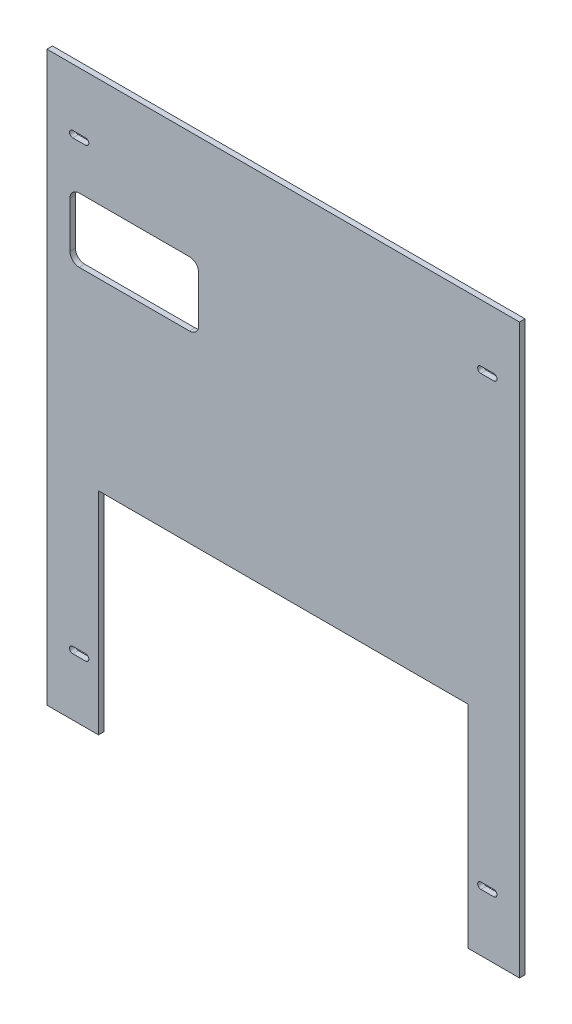
SolidWorks part; units mm, degrees
ref_plane "Plan de face" through (0, 0, 0) normal (0, 0, 1) x (1, 0, 0)
ref_plane "Plan de dessus" through (0, 0, 0) normal (0, 1, 0) x (1, 0, 0)
ref_plane "Plan de droite" through (0, 0, 0) normal (1, 0, 0) x (0, 0, -1)
sketch "Esquisse1" plane through (0, 0, 0) normal (0, 0, 1) x (1, 0, 0)
  line L0 (0, 154.5) -> (0, -154.5) construction
  line L1 (128.5, 154.5) -> (-128.5, 154.5)
  line L2 (128.5, 154.5) -> (128.5, -154.5)
  line L3 (128.5, -154.5) -> (-128.5, -154.5)
  line L4 (-128.5, 154.5) -> (-128.5, -154.5)
  line L5 (128.5, 154.5) -> (-128.5, -154.5) construction
  line L6 (128.5, -154.5) -> (-128.5, 154.5) construction
  line L7 (-111, 121.5) -> (0, 121.5) construction
  line L8 (-128.5, 0) -> (128.5, 0) construction
  line L9 (-114.5, 121.5) -> (-107.5, 121.5) construction
  line L10 (-114.5, 123.25) -> (-107.5, 123.25)
  line L11 (-114.5, 119.75) -> (-107.5, 119.75)
  line L12 (107.5, -121.5) -> (114.5, -121.5) construction
  line L13 (107.5, -119.75) -> (114.5, -119.75)
  line L14 (107.5, -123.25) -> (114.5, -123.25)
  line L15 (-114.5, -121.5) -> (-107.5, -121.5) construction
  line L16 (-114.5, -119.75) -> (-107.5, -119.75)
  line L17 (-114.5, -123.25) -> (-107.5, -123.25)
  line L18 (107.5, 121.5) -> (114.5, 121.5) construction
  line L19 (107.5, 123.25) -> (114.5, 123.25)
  line L20 (107.5, 119.75) -> (114.5, 119.75)
  circle A0 centre (-111, 121.5) radius 1.75 construction
  circle A1 centre (111, 121.5) radius 1.75 construction
  circle A2 centre (111, -121.5) radius 1.75 construction
  circle A3 centre (-111, -121.5) radius 1.75 construction
  arc A4 (-114.5, 123.25) -> (-114.5, 119.75) centre (-114.5, 121.5) ccw
  arc A5 (-107.5, 119.75) -> (-107.5, 123.25) centre (-107.5, 121.5) ccw
  arc A6 (107.5, -119.75) -> (107.5, -123.25) centre (107.5, -121.5) ccw
  arc A7 (114.5, -123.25) -> (114.5, -119.75) centre (114.5, -121.5) ccw
  arc A8 (-114.5, -119.75) -> (-114.5, -123.25) centre (-114.5, -121.5) ccw
  arc A9 (-107.5, -123.25) -> (-107.5, -119.75) centre (-107.5, -121.5) ccw
  arc A10 (107.5, 123.25) -> (107.5, 119.75) centre (107.5, 121.5) ccw
  arc A11 (114.5, 119.75) -> (114.5, 123.25) centre (114.5, 121.5) ccw
  point P0 (0, 0)
  point P21 (-111, 121.5)
  point P28 (111, -121.5)
  point P35 (-111, -121.5)
  point P42 (111, 121.5)
  point P47 (0, 0)
  point P48 (0, 0)
  point P49 (0, 0)
  point P50 (0, 0)
  dimension "D3" = 3.5
  dimension "D7" = 1.75
  dimension "D9" = 1.75
  dimension "D11" = 1.75
  dimension "D13" = 1.75
  dimension "D1" = 257
  dimension "D2" = 309
  dimension "D4" = 111
  dimension "D5" = 33
  dimension "D6" = 7
  dimension "D8" = 7
  dimension "D10" = 7
  dimension "D12" = 7
extrude "Boss.-Extru.1" add sketch "Esquisse1" along normal blind 3
sketch "Esquisse2" plane through (0, 0, 3) normal (0, 0, 1) x (1, 0, 0)
  line L0 (-128.5, -154.5) -> (128.5, -154.5) construction
  line L1 (-100.5, -154.5) -> (100.5, -154.5)
  line L2 (-100.5, -154.5) -> (-100.5, -39.5)
  line L3 (-100.5, -39.5) -> (100.5, -39.5)
  line L4 (100.5, -154.5) -> (100.5, -39.5)
  point P6 (0, -154.5)
  point P7 (0, -154.5)
  dimension "D1" = 201
  dimension "D2" = 115
extrude "Enlèv. mat.-Extru.1" cut sketch "Esquisse2" against normal through all
sketch "Esquisse3" plane through (0, 0, 3) normal (0, 0, 1) x (1, 0, 0)
  line L0 (128.5, 154.5) -> (-128.5, 154.5) construction
  line L1 (-111, 60.5) -> (-51, 60.5)
  line L2 (-116, 65.5) -> (-116, 90.5)
  line L3 (-111, 95.5) -> (-51, 95.5)
  line L4 (-46, 65.5) -> (-46, 90.5)
  line L5 (-128.5, 154.5) -> (-128.5, -154.5) construction
  arc A0 (-111, 60.5) -> (-116, 65.5) centre (-111, 65.5) cw
  arc A1 (-51, 60.5) -> (-46, 65.5) centre (-51, 65.5) ccw
  arc A2 (-51, 95.5) -> (-46, 90.5) centre (-51, 90.5) cw
  arc A3 (-116, 90.5) -> (-111, 95.5) centre (-111, 90.5) cw
  point P10 (-116, 60.5)
  point P15 (-46, 95.5)
  point P18 (-116, 95.5)
  dimension "D5" = 5
  dimension "D1" = 94
  dimension "D2" = 70
  dimension "D3" = 12.5
  dimension "D4" = 35
extrude "Enlèv. mat.-Extru.2" cut sketch "Esquisse3" against normal through all
